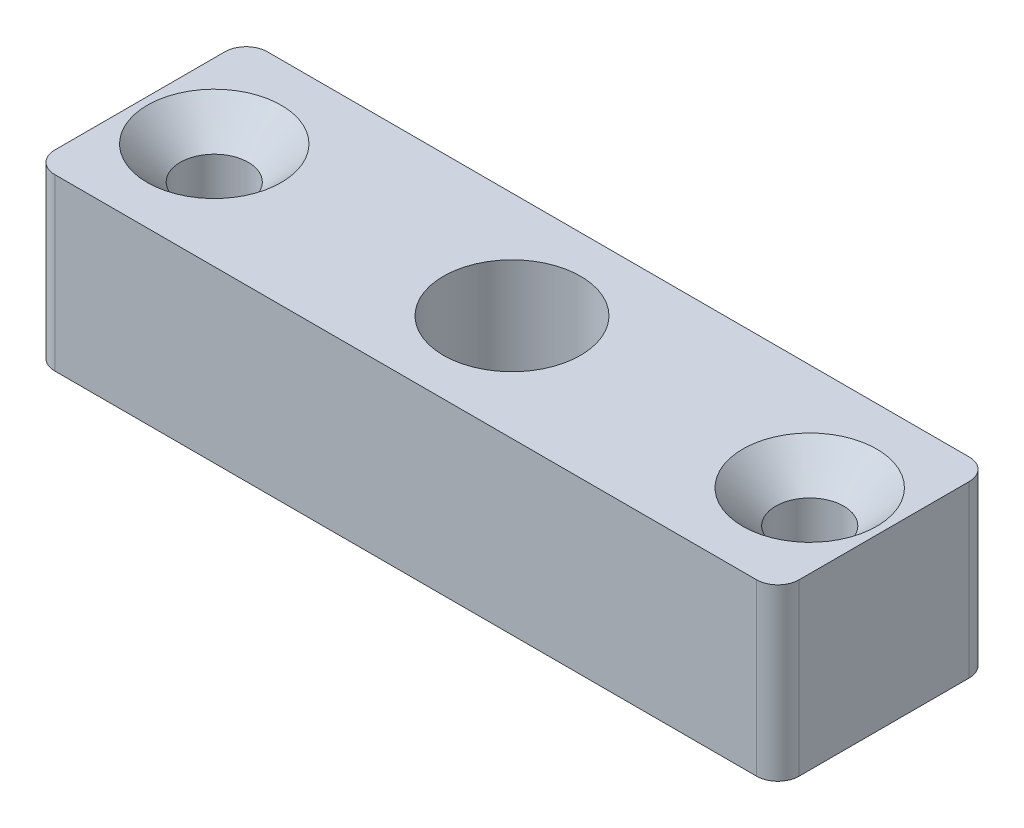
SolidWorks part; units mm, degrees
material "ABS"
ref_plane "Front Plane" through (0, 0, 0) normal (0, 0, 1) x (1, 0, 0)
ref_plane "Top Plane" through (0, 0, 0) normal (0, 1, 0) x (1, 0, 0)
ref_plane "Right Plane" through (0, 0, 0) normal (1, 0, 0) x (0, 0, -1)
sketch "Sketch1" plane through (0, 0, 0) normal (0, 1, 0) x (1, 0, 0)
  line L0 (-14, 0) -> (14, 0) construction
  line L1 (-17.5, 5) -> (17.5, 5)
  line L2 (-17.5, 5) -> (-17.5, -5)
  line L3 (-17.5, -5) -> (17.5, -5)
  line L4 (17.5, 5) -> (17.5, -5)
  line L5 (-2.25, 3) -> (2.25, 3) construction
  line L6 (-2.25, 3) -> (-2.25, -5) construction
  line L7 (-2.25, -5) -> (2.25, -5) construction
  line L8 (2.25, 3) -> (2.25, -5) construction
  circle A0 centre (-14, 0) radius 1.5 construction
  circle A1 centre (14, 0) radius 1.5 construction
  circle A2 centre (0, 0) radius 3.225
  point P4 (0, 5)
  point P6 (-17.5, 0)
  point P11 (0, 3)
  point P18 (0, 0)
  dimension "D6" = 3
  dimension "D7" = 6.45
  dimension "D1" = 35
  dimension "D2" = 10
  dimension "D3" = 4.5
  dimension "D4" = 2
  dimension "D5" = 28
extrude "Boss-Extrude1" add sketch "Sketch1" against normal blind 8 contours L3 L4 L1 L2
hole_wizard "CSK for M3 Flat Head Machine Screw1" positions "3DSketch1" profile "Sketch3" countersink size "M3" standard "ANSI Metric" end condition through all
sketch3d "3DSketch1"
  point P0 (-14, 0, 0)
  point P2 (14, 0, 0)
sketch "Sketch3" plane through (-14, 0, 0) normal (1, 0, 0) x (0, 0, 1)
  line L0 (0, 0) -> (0, 8)
  line L1 (0, 8) -> (1.6, 8)
  line L2 (1.6, 8) -> (1.6, 1.55)
  line L3 (1.6, 1.55) -> (3.15, 0)
  line L5 (3.15, 0) -> (0, 0)
  line L6 (-1.6, 1.55) -> (-3.15, 0) construction
  line L11 (0, -6.35) -> (0, 107.95) construction
  dimension "Thru Hole Dia." = 3.2
  dimension "Thru Hole Depth" = 8
  dimension "Near C'Sink Dia." = 6.3
  dimension "Near C'Sink Angle" = 90
extrude "Cut-Extrude2" cut sketch "Sketch1<3>" against normal blind 6.35 contours A2
sketch "Sketch1<3>" plane through (0, 0, 0) normal (0, 1, 0) x (1, 0, 0) same geometry as "Sketch1"
fillet "Fillet1" radius 1 4 edges at (17.5, -4, -5) (17.5, -4, 5) (-17.5, -4, -5) (-17.5, -4, 5)
